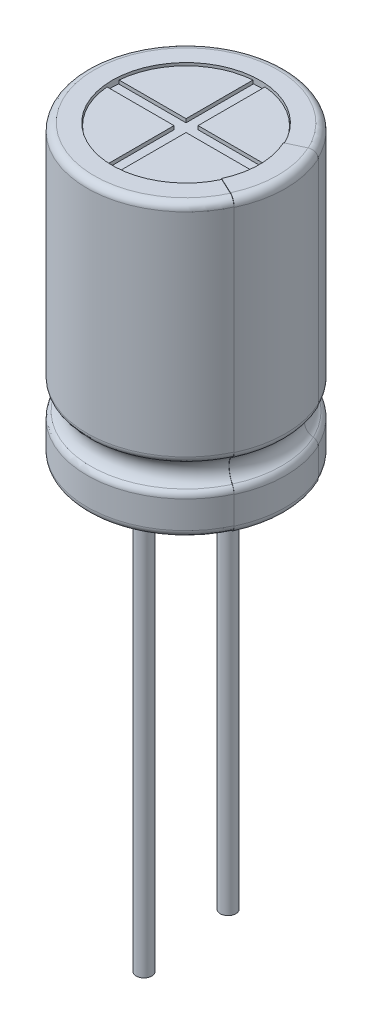
SolidWorks part; units mm, degrees
note: The reader was unsure of these and kept them because the rebuilt part matched: shared geometry of "Sketch7<4>".
ref_plane "Front Plane" through (0, 0, 0) normal (0, 0, 1) x (1, 0, 0)
ref_plane "Top Plane" through (0, 0, 0) normal (0, 1, 0) x (1, 0, 0)
ref_plane "Right Plane" through (0, 0, 0) normal (1, 0, 0) x (0, 0, -1)
sketch "Sketch1" plane through (0, 0, 0) normal (0, 0, 1) x (1, 0, 0)
  line L8 (0, 0.6) -> (3.125, 0.6)
  line L9 (3.125, 0.6) -> (3.125, 0.4)
  line L10 (3.125, 0.4) -> (3.825, 0.4)
  line L11 (4.125, 0.7) -> (4.125, 1.8415)
  line L12 (3.825, 12.5) -> (3.075, 12.5)
  line L13 (3.075, 12.5) -> (3.075, 12.25)
  line L14 (3.075, 12.25) -> (0, 12.25)
  line L15 (0, 12.25) -> (0, 0.6)
  line L16 (1.2518, 2.6) -> (5.492, 2.6) construction
  line L17 (4.125, 3.3585) -> (4.125, 12.2)
  arc A0 (3.825, 0.4) -> (4.125, 0.7) centre (3.825, 0.7) ccw
  arc A1 (4.125, 12.2) -> (3.825, 12.5) centre (3.825, 12.2) ccw
  arc A2 (3.9781, 3.1005) -> (3.9781, 2.0995) centre (4.275, 2.6) ccw
  arc A3 (4.125, 1.8415) -> (3.9781, 2.0995) centre (3.825, 1.8415) ccw
  arc A4 (4.125, 3.3585) -> (3.9781, 3.1005) centre (3.825, 3.3585) cw
  point P10 (0, 0)
  dimension "D8" = 0.3
  dimension "D11" = 1.1639
  dimension "D12" = 0.3
  dimension "D1" = 11.65
  dimension "D2" = 0.2
  dimension "D3" = 0.6
  dimension "D4" = 3.075
  dimension "D5" = 1.05
  dimension "D6" = 0.25
  dimension "D7" = 1
  dimension "D9" = 2.2
  dimension "D10" = 0.15
revolve "Revolve1" add sketch "Sketch1" angle 360 about L15
sketch "Sketch2" plane through (0, 12.25, 0) normal (0, 1, 0) x (1, 0, 0)
  line L0 (-0.25, 0.25) -> (-0.25, 3.0397)
  line L2 (0.25, -3.0397) -> (0.25, -0.25)
  line L4 (-0.25, -3.0397) -> (-0.25, -0.25)
  line L5 (0.25, 0.25) -> (0.25, 3.0397)
  line L7 (3.0397, -0.25) -> (0.25, -0.25)
  line L9 (3.0397, 0.25) -> (0.25, 0.25)
  line L13 (-0.25, -0.25) -> (-3.0397, -0.25)
  line L16 (-0.25, 0.25) -> (-3.0397, 0.25)
  arc A0 (0.25, -3.0397) -> (3.0397, -0.25) centre (0, 0) ccw
  arc A1 (3.0397, 0.25) -> (0.25, 3.0397) centre (0, 0) ccw
  arc A2 (-0.25, 3.0397) -> (-3.0397, 0.25) centre (0, 0) ccw
  arc A3 (-3.0397, -0.25) -> (-0.25, -3.0397) centre (0, 0) ccw
  dimension "D3" = 3.05
  dimension "D1" = 0.5
  dimension "D2" = 0.5
  dimension "D4" = 0.25
  dimension "D5" = 0.25
  dimension "D6" = 0.5
extrude "Boss-Extrude1" add sketch "Sketch2" along normal blind 0.15 separate body
sketch "Sketch3" plane through (0, 0.6, 0) normal (0, -1, 0) x (1, 0, 0)
  circle A0 centre (0, 0) radius 2.5
  ellipse E0 centre (0, 0) end of major axis (-2.2, 0) minor radius 1.7
  dimension "D1" = 5
extrude "Boss-Extrude2" add sketch "Sketch3" along normal blind 0.6 separate body
sketch "Sketch4" plane through (0, 0.6, 0) normal (0, -1, 0) x (1, 0, 0)
sketch "Sketch5" plane through (0, 0, 0) normal (0, 0, 1) x (1, 0, 0)
  line L8 (3.075, 12.5) -> (3.825, 12.5)
  line L10 (4.125, 3.3585) -> (4.125, 12.2) construction
  line L11 (4.125, 12.2) -> (4.125, 3.3585)
  line L12 (3.075, 12.5) -> (3.125, 0.4)
  line L13 (3.125, 0.4) -> (3.825, 0.4)
  line L14 (0, 0) -> (0, 15.0032) construction
  line L15 (4.145, 12.2) -> (4.145, 3.3585)
  line L16 (4.125, 0.7) -> (4.125, 1.8415)
  line L17 (4.145, 0.7) -> (4.145, 1.8415)
  line L18 (3.1051, 0.38) -> (3.825, 0.38)
  line L19 (3.0549, 12.52) -> (3.1051, 0.38)
  line L20 (3.0549, 12.52) -> (3.825, 12.52)
  arc A5 (3.825, 12.5) -> (4.125, 12.2) centre (3.825, 12.2) cw
  arc A6 (3.825, 0.4) -> (4.125, 0.7) centre (3.825, 0.7) ccw construction
  arc A7 (4.125, 1.8415) -> (3.9781, 2.0995) centre (3.825, 1.8415) ccw
  arc A8 (4.125, 3.3585) -> (3.9781, 3.1005) centre (3.825, 3.3585) cw
  arc A9 (3.9781, 3.1005) -> (3.9781, 2.0995) centre (4.275, 2.6) ccw
  arc A10 (4.125, 0.7) -> (3.825, 0.4) centre (3.825, 0.7) cw
  arc A11 (3.825, 12.52) -> (4.145, 12.2) centre (3.825, 12.2) cw
  arc A12 (4.145, 3.3585) -> (3.9883, 3.0833) centre (3.825, 3.3585) cw
  arc A13 (3.9883, 3.0833) -> (3.9883, 2.1167) centre (4.275, 2.6) ccw
  arc A14 (4.145, 1.8415) -> (3.9883, 2.1167) centre (3.825, 1.8415) ccw
  arc A15 (4.145, 0.7) -> (3.825, 0.38) centre (3.825, 0.7) cw
  dimension "D1" = 0.02
revolve "Revolve3" add sketch "Sketch5" angle 25 about L14
sketch "Sketch7" plane through (0, 0.6, 0) normal (0, -1, 0) x (1, 0, 0)
  line L0 (-1.4523, 0) -> (1.4342, 0) construction
  line L1 (0, 0) -> (0, 0.7626) construction
  circle A0 centre (-1.75, 0) radius 0.325
  circle A2 centre (1.75, 0) radius 0.325
  dimension "D2" = 0.65
  dimension "D1" = 1.75
extrude "Boss-Extrude3" add sketch "Sketch7" along normal blind 19.6 contours A0
extrude "Boss-Extrude4" add sketch "Sketch7<4>" along normal blind 15.6 contours A2
sketch "Sketch7<4>" plane through (0, 0.6, 0) normal (0, -1, 0) x (1, 0, 0) same geometry as "Sketch7"
